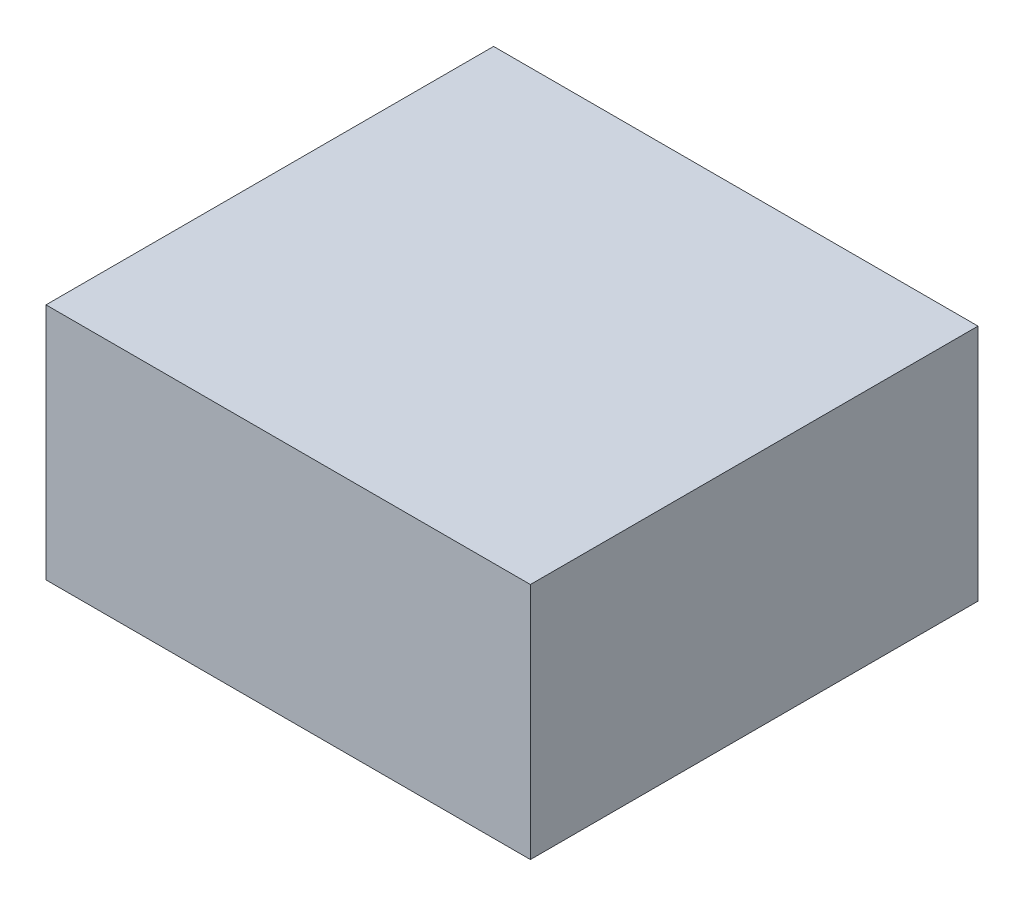
SolidWorks part; units mm, degrees
ref_plane "Front Plane" through (0, 0, 0) normal (0, 0, 1) x (1, 0, 0)
ref_plane "Top Plane" through (0, 0, 0) normal (0, 1, 0) x (1, 0, 0)
ref_plane "Right Plane" through (0, 0, 0) normal (1, 0, 0) x (0, 0, -1)
sketch "Sketch1" plane through (0, 0, 0) normal (0, 1, 0) x (1, 0, 0)
  line L1 (77.216, -71.3486) -> (-77.216, -71.3486)
  line L2 (77.216, -71.3486) -> (77.216, 71.3486)
  line L3 (77.216, 71.3486) -> (-77.216, 71.3486)
  line L4 (-77.216, -71.3486) -> (-77.216, 71.3486)
  line L5 (77.216, -71.3486) -> (-77.216, 71.3486) construction
  line L6 (77.216, 71.3486) -> (-77.216, -71.3486) construction
  point P0 (0, 0)
  point P5 (0, 0)
  dimension "D1" = 142.6972
  dimension "D2" = 154.432
extrude "Boss-Extrude1" add sketch "Sketch1" along normal blind 75.946
